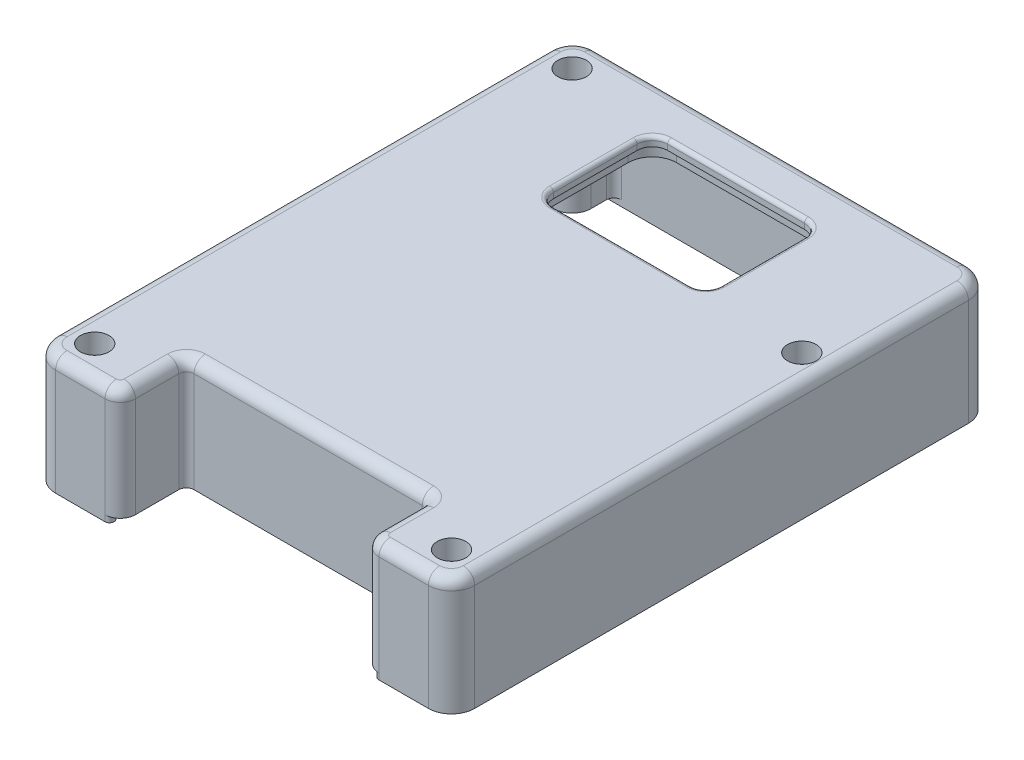
SolidWorks part; units mm, degrees
ref_plane "Front Plane" through (0, 0, 0) normal (0, 0, 1) x (1, 0, 0)
ref_plane "Top Plane" through (0, 0, 0) normal (0, 1, 0) x (1, 0, 0)
ref_plane "Right Plane" through (0, 0, 0) normal (1, 0, 0) x (0, 0, -1)
sketch "Esquisse1" plane through (0, 0, 0) normal (0, 1, 0) x (1, 0, 0)
  line L0 (-20.9, 31.3) -> (-20.9, 33.3)
  line L1 (-19.9, 34.3) -> (23.35, 34.3)
  line L2 (-26.35, 27.8) -> (-26.35, -27.9)
  line L3 (-19.95, -34.3) -> (-18.2, -34.3)
  line L4 (26.35, 31.3) -> (26.35, 17.55)
  line L5 (-26.35, 34.3) -> (26.35, -34.3) construction
  line L6 (-26.35, -34.3) -> (26.35, 34.3) construction
  line L7 (-24.5, 35.5) -> (24.5, 35.5)
  line L8 (-27.55, 32.45) -> (-27.55, -32.45)
  line L9 (-24.5, -35.5) -> (-18, -35.5)
  line L10 (27.55, 32.45) -> (27.55, -32.45)
  line L11 (-23.4, 28.8) -> (-25.35, 28.8)
  line L12 (20.95, -31.4) -> (20.95, -33.3)
  line L13 (23.45, -28.9) -> (25.35, -28.9)
  line L14 (-20.95, -31.4) -> (-20.95, -33.3)
  line L15 (-23.45, -28.9) -> (-25.35, -28.9)
  line L16 (24.05, 16.55) -> (25.35, 16.55)
  line L17 (24.05, 11.55) -> (25.35, 11.55)
  line L18 (26.35, 10.55) -> (26.35, -27.9)
  line L19 (0, 0) -> (0, -34.3) construction
  line L20 (0, -26.8) -> (15, -26.8)
  line L21 (0, -26.8) -> (-15, -26.8)
  line L22 (-16, -27.8) -> (-16, -33.5)
  line L23 (16, -27.8) -> (16, -33.5)
  line L24 (18, -35.5) -> (24.5, -35.5)
  line L25 (18.2, -34.3) -> (19.95, -34.3)
  line L26 (-17.2, -33.3) -> (-17.2, -26.6)
  line L27 (-16.2, -25.6) -> (16.2, -25.6)
  line L28 (17.2, -26.6) -> (17.2, -33.3)
  circle A0 centre (-23.45, -31.4) radius 1.1
  circle A1 centre (23.45, -31.4) radius 1.1
  circle A2 centre (-23.4, 31.3) radius 1.1
  circle A3 centre (24.05, 14.05) radius 1.1
  arc A4 (-23.4, 28.8) -> (-20.9, 31.3) centre (-23.4, 31.3) ccw
  arc A5 (-20.95, -31.4) -> (-23.45, -28.9) centre (-23.45, -31.4) ccw
  arc A6 (23.45, -28.9) -> (20.95, -31.4) centre (23.45, -31.4) ccw
  arc A7 (24.05, 16.55) -> (24.05, 11.55) centre (24.05, 14.05) ccw
  arc A8 (-27.55, -32.45) -> (-24.5, -35.5) centre (-24.5, -32.45) ccw
  arc A9 (24.5, -35.5) -> (27.55, -32.45) centre (24.5, -32.45) ccw
  arc A10 (24.5, 35.5) -> (27.55, 32.45) centre (24.5, 32.45) cw
  arc A11 (-24.5, 35.5) -> (-27.55, 32.45) centre (-24.5, 32.45) ccw
  arc A12 (23.35, 34.3) -> (26.35, 31.3) centre (23.35, 31.3) cw
  arc A13 (-25.35, 28.8) -> (-26.35, 27.8) centre (-25.35, 27.8) ccw
  arc A14 (-20.9, 33.3) -> (-19.9, 34.3) centre (-19.9, 33.3) cw
  arc A15 (25.35, -28.9) -> (26.35, -27.9) centre (25.35, -27.9) ccw
  arc A16 (20.95, -33.3) -> (19.95, -34.3) centre (19.95, -33.3) cw
  arc A17 (-20.95, -33.3) -> (-19.95, -34.3) centre (-19.95, -33.3) ccw
  arc A18 (-25.35, -28.9) -> (-26.35, -27.9) centre (-25.35, -27.9) cw
  arc A19 (25.35, 11.55) -> (26.35, 10.55) centre (25.35, 10.55) cw
  arc A20 (25.35, 16.55) -> (26.35, 17.55) centre (25.35, 17.55) ccw
  arc A21 (-17.2, -33.3) -> (-18.2, -34.3) centre (-18.2, -33.3) cw
  arc A22 (17.2, -33.3) -> (18.2, -34.3) centre (18.2, -33.3) ccw
  arc A23 (16, -33.5) -> (18, -35.5) centre (18, -33.5) ccw
  arc A24 (-16, -33.5) -> (-18, -35.5) centre (-18, -33.5) cw
  arc A25 (-17.2, -26.6) -> (-16.2, -25.6) centre (-16.2, -26.6) cw
  arc A26 (16.2, -25.6) -> (17.2, -26.6) centre (16.2, -26.6) cw
  arc A27 (15, -26.8) -> (16, -27.8) centre (15, -27.8) cw
  arc A28 (-15, -26.8) -> (-16, -27.8) centre (-15, -27.8) ccw
  point P0 (0, 0)
  point P59 (26.35, 11.55)
  point P79 (16, -35.5)
  dimension "D7" = 2.2
  dimension "D8" = 2.2
  dimension "D9" = 2.2
  dimension "D10" = 2.2
  dimension "D19" = 5
  dimension "D20" = 5
  dimension "D21" = 5
  dimension "D22" = 5
  dimension "D23" = 3.05
  dimension "D24" = 3
  dimension "D25" = 1
  dimension "D34" = 1
  dimension "D35" = 2
  dimension "D36" = 1
  dimension "D1" = 52.7
  dimension "D2" = 68.6
  dimension "D3" = 1.2
  dimension "D4" = 1.2
  dimension "D5" = 1.2
  dimension "D6" = 1.2
  dimension "D11" = 2.9
  dimension "D12" = 2.9
  dimension "D13" = 2.9
  dimension "D14" = 2.9
  dimension "D15" = 48.35
  dimension "D16" = 2.3
  dimension "D17" = 2.95
  dimension "D18" = 3
  dimension "D28" = 7.5
  dimension "D29" = 11.55
  dimension "D30" = 11.55
  dimension "D31" = 1.2
  dimension "D32" = 1.2
  dimension "D33" = 1.2
extrude "Boss.-Extru.1" add sketch "Esquisse1" along normal blind 13.5
sketch "Esquisse2" plane through (0, 13.5, 0) normal (0, 1, 0) x (1, 0, 0)
  line L16 (-24.5, -35.5) -> (-18, -35.5)
  line L17 (-16, -33.5) -> (-16, -27.8)
  line L18 (-15, -26.8) -> (15, -26.8)
  line L19 (16, -27.8) -> (16, -33.5)
  line L20 (18, -35.5) -> (24.5, -35.5)
  line L21 (27.55, -32.45) -> (27.55, 32.45)
  line L22 (24.5, 35.5) -> (-24.5, 35.5)
  line L23 (-27.55, 32.45) -> (-27.55, -32.45)
  line L24 (-24.5, -35.5) -> (-18, -35.5)
  line L25 (-16, -33.5) -> (-16, -27.8)
  line L26 (-15, -26.8) -> (15, -26.8)
  line L27 (16, -27.8) -> (16, -33.5)
  line L28 (18, -35.5) -> (24.5, -35.5)
  line L29 (27.55, -32.45) -> (27.55, 32.45)
  line L30 (24.5, 35.5) -> (-24.5, 35.5)
  line L31 (-27.55, 32.45) -> (-27.55, -32.45)
  arc A16 (-27.55, -32.45) -> (-24.5, -35.5) centre (-24.5, -32.45) ccw
  arc A17 (-18, -35.5) -> (-16, -33.5) centre (-18, -33.5) ccw
  arc A18 (-15, -26.8) -> (-16, -27.8) centre (-15, -27.8) ccw
  arc A19 (16, -27.8) -> (15, -26.8) centre (15, -27.8) ccw
  arc A20 (16, -33.5) -> (18, -35.5) centre (18, -33.5) ccw
  arc A21 (24.5, -35.5) -> (27.55, -32.45) centre (24.5, -32.45) ccw
  arc A22 (27.55, 32.45) -> (24.5, 35.5) centre (24.5, 32.45) ccw
  arc A23 (-24.5, 35.5) -> (-27.55, 32.45) centre (-24.5, 32.45) ccw
  arc A24 (-27.55, -32.45) -> (-24.5, -35.5) centre (-24.5, -32.45) ccw
  arc A25 (-18, -35.5) -> (-16, -33.5) centre (-18, -33.5) ccw
  arc A26 (-15, -26.8) -> (-16, -27.8) centre (-15, -27.8) ccw
  arc A27 (16, -27.8) -> (15, -26.8) centre (15, -27.8) ccw
  arc A28 (16, -33.5) -> (18, -35.5) centre (18, -33.5) ccw
  arc A29 (24.5, -35.5) -> (27.55, -32.45) centre (24.5, -32.45) ccw
  arc A30 (27.55, 32.45) -> (24.5, 35.5) centre (24.5, 32.45) ccw
  arc A31 (-24.5, 35.5) -> (-27.55, 32.45) centre (-24.5, 32.45) ccw
  dimension "D1" = 0
extrude "Boss.-Extru.2" add sketch "Esquisse2" along normal blind 1.2
fillet "Congé1" radius 1.5 16 edges at (-27.55, 14.7, 0) (-26.6567, 14.7, -34.6067) (0, 14.7, -35.5) (26.6567, 14.7, -34.6067) (27.55, 14.7, 0) (26.6567, 14.7, 34.6067) (21.25, 14.7, 35.5) (16.5858, 14.7, 34.9142) (16, 14.7, 30.65) (15.7071, 14.7, 27.0929) (0, 14.7, 26.8) (-15.7071, 14.7, 27.0929) (-16, 14.7, 30.65) (-16.5858, 14.7, 34.9142) (-21.25, 14.7, 35.5) (-26.6567, 14.7, 34.6067)
sketch "Esquisse3" plane through (0, 0, 0) normal (0, -1, 0) x (1, 0, 0)
  line L8 (-26.35, 32.45) -> (-26.35, -32.45)
  line L9 (-24.5, -34.3) -> (24.5, -34.3)
  line L10 (26.35, -32.45) -> (26.35, 32.45)
  line L11 (24.5, 34.3) -> (18, 34.3)
  line L12 (17.2, 33.5) -> (17.2, 27.8)
  line L13 (15, 25.6) -> (-15, 25.6)
  line L14 (-17.2, 27.8) -> (-17.2, 33.5)
  line L15 (-18, 34.3) -> (-24.5, 34.3)
  line L16 (-27.55, 32.45) -> (-27.55, -32.45)
  line L17 (-24.5, -35.5) -> (24.5, -35.5)
  line L18 (27.55, -32.45) -> (27.55, 32.45)
  line L19 (24.5, 35.5) -> (18, 35.5)
  line L20 (16, 33.5) -> (16, 27.8)
  line L21 (15, 26.8) -> (-15, 26.8)
  line L22 (-16, 27.8) -> (-16, 33.5)
  line L23 (-18, 35.5) -> (-24.5, 35.5)
  line L24 (-27.55, 32.45) -> (-27.55, -32.45)
  line L25 (-24.5, -35.5) -> (24.5, -35.5)
  line L26 (27.55, -32.45) -> (27.55, 32.45)
  line L27 (24.5, 35.5) -> (18, 35.5)
  line L28 (16, 33.5) -> (16, 27.8)
  line L29 (15, 26.8) -> (-15, 26.8)
  line L30 (-16, 27.8) -> (-16, 33.5)
  line L31 (-18, 35.5) -> (-24.5, 35.5)
  arc A8 (-26.35, -32.45) -> (-24.5, -34.3) centre (-24.5, -32.45) ccw
  arc A9 (24.5, -34.3) -> (26.35, -32.45) centre (24.5, -32.45) ccw
  arc A10 (26.35, 32.45) -> (24.5, 34.3) centre (24.5, 32.45) ccw
  arc A11 (18, 34.3) -> (17.2, 33.5) centre (18, 33.5) ccw
  arc A12 (15, 25.6) -> (17.2, 27.8) centre (15, 27.8) ccw
  arc A13 (-17.2, 27.8) -> (-15, 25.6) centre (-15, 27.8) ccw
  arc A14 (-17.2, 33.5) -> (-18, 34.3) centre (-18, 33.5) ccw
  arc A15 (-24.5, 34.3) -> (-26.35, 32.45) centre (-24.5, 32.45) ccw
  arc A16 (-24.5, 35.5) -> (-27.55, 32.45) centre (-24.5, 32.45) ccw
  arc A17 (-27.55, -32.45) -> (-24.5, -35.5) centre (-24.5, -32.45) ccw
  arc A18 (24.5, -35.5) -> (27.55, -32.45) centre (24.5, -32.45) ccw
  arc A19 (27.55, 32.45) -> (24.5, 35.5) centre (24.5, 32.45) ccw
  arc A20 (18, 35.5) -> (16, 33.5) centre (18, 33.5) ccw
  arc A21 (15, 26.8) -> (16, 27.8) centre (15, 27.8) ccw
  arc A22 (-16, 27.8) -> (-15, 26.8) centre (-15, 27.8) ccw
  arc A23 (-16, 33.5) -> (-18, 35.5) centre (-18, 33.5) ccw
  arc A24 (-24.5, 35.5) -> (-27.55, 32.45) centre (-24.5, 32.45) ccw
  arc A25 (-27.55, -32.45) -> (-24.5, -35.5) centre (-24.5, -32.45) ccw
  arc A26 (24.5, -35.5) -> (27.55, -32.45) centre (24.5, -32.45) ccw
  arc A27 (27.55, 32.45) -> (24.5, 35.5) centre (24.5, 32.45) ccw
  arc A28 (18, 35.5) -> (16, 33.5) centre (18, 33.5) ccw
  arc A29 (15, 26.8) -> (16, 27.8) centre (15, 27.8) ccw
  arc A30 (-16, 27.8) -> (-15, 26.8) centre (-15, 27.8) ccw
  arc A31 (-16, 33.5) -> (-18, 35.5) centre (-18, 33.5) ccw
  dimension "D1" = 0
  dimension "D2" = 1.2
extrude "Boss.-Extru.3" add sketch "Esquisse3" along normal blind 0.8
sketch "Esquisse4" plane through (0, -0.8, 0) normal (0, -1, 0) x (-1, 0, 0)
  line L0 (18, -34.3) -> (24.5, -34.3) construction
  line L1 (18.8331, -34.3) -> (-18.8435, -34.3)
  line L2 (18.8331, -34.3) -> (18.8331, -23.8135)
  line L3 (18.8331, -23.8135) -> (-18.8435, -23.8135)
  line L4 (-18.8435, -34.3) -> (-18.8435, -23.8135)
extrude "Enlèv. mat.-Extru.1" cut sketch "Esquisse4" against normal blind 0.8
fillet "Congé2" radius 0.6 2 edges at (16.167, -0.4, 34.3) (-16.167, -0.4, 34.3)
sketch "Esquisse5" plane through (0, 13.5, 0) normal (0, -1, 0) x (1, 0, 0)
  circle A0 centre (-23.45, 31.4) radius 1.25
  circle A1 centre (23.45, 31.4) radius 1.25
  circle A2 centre (24.05, -14.05) radius 1.25
  circle A3 centre (-23.4, -31.3) radius 1.25
extrude "Enlèv. mat.-Extru.2" cut sketch "Esquisse5" against normal through all
sketch "Esquisse6" plane through (0, 14.7, 0) normal (0, 1, 0) x (1, 0, 0)
  circle A0 centre (-23.4, 31.3) radius 1.875
  circle A1 centre (24.05, 14.05) radius 1.875
  circle A2 centre (23.45, -31.4) radius 1.875
  circle A3 centre (-23.45, -31.4) radius 1.875
  dimension "D1" = 3.75
  dimension "D2" = 3.75
  dimension "D3" = 3.75
  dimension "D4" = 3.75
extrude "Enlèv. mat.-Extru.3" cut sketch "Esquisse6" against normal blind 3.3
fillet "Congé3" radius 0.6 34 edges at (24.7, 13.5, -11.55) (26.0571, 13.5, -11.2571) (26.35, 13.5, 8.675) (26.0571, 13.5, 28.6071) (24.4, 13.5, 28.9) (21.6822, 13.5, 29.6322) (20.95, 13.5, 32.35) (20.6571, 13.5, 34.0071) (19.075, 13.5, 34.3) (17.4929, 13.5, 34.0071) (17.2, 13.5, 29.95) (16.9071, 13.5, 25.8929) (0, 13.5, 25.6) (-16.9071, 13.5, 25.8929) (-17.2, 13.5, 29.95) (-17.4929, 13.5, 34.0071) (-19.075, 13.5, 34.3) (-20.6571, 13.5, 34.0071) (-20.95, 13.5, 32.35) (-21.6822, 13.5, 29.6322) (-24.4, 13.5, 28.9) (-26.0571, 13.5, 28.6071) (-26.35, 13.5, 0.05) (-26.0571, 13.5, -28.5071) (-24.375, 13.5, -28.8) (-21.6322, 13.5, -29.5322) (-20.9, 13.5, -32.3) (-20.6071, 13.5, -34.0071) (1.725, 13.5, -34.3) (25.4713, 13.5, -33.4213) (26.35, 13.5, -24.425) (26.0571, 13.5, -16.8429) (24.7, 13.5, -16.55) (21.55, 13.5, -14.05)
fillet "Congé4" radius 0.7 4 edges at (-23.45, 11.4, 33.275) (23.45, 11.4, 33.275) (-23.4, 11.4, -29.425) (24.05, 11.4, -12.175)
sketch "Esquisse7" plane through (0, 13.5, 0) normal (0, -1, 0) x (1, 0, 0)
  line L0 (0, 0) -> (0, -34.3) construction
  line L1 (23.35, -34.3) -> (-19.9, -34.3) construction
  line L3 (-9, -14.45) -> (9, -14.45)
  line L4 (-11, -16.45) -> (-11, -27.45)
  line L5 (-9, -29.45) -> (9, -29.45)
  line L6 (11, -16.45) -> (11, -27.45)
  line L7 (-11, -14.45) -> (11, -29.45) construction
  line L8 (-11, -29.45) -> (11, -14.45) construction
  arc A0 (9, -14.45) -> (11, -16.45) centre (9, -16.45) cw
  arc A1 (9, -29.45) -> (11, -27.45) centre (9, -27.45) ccw
  arc A2 (-11, -27.45) -> (-9, -29.45) centre (-9, -27.45) ccw
  arc A3 (-9, -14.45) -> (-11, -16.45) centre (-9, -16.45) ccw
  point P5 (0, -21.95)
  dimension "D4" = 2
  dimension "D1" = 12.35
  dimension "D2" = 15
  dimension "D3" = 22
extrude "Enlèv. mat.-Extru.4" cut sketch "Esquisse7" against normal blind 10
sketch "Esquisse8" plane through (0, 13.5, 0) normal (0, -1, 0) x (1, 0, 0)
  line L20 (-13.4, -16.45) -> (-13.4, -27.45)
  line L21 (-9, -31.85) -> (9, -31.85)
  line L22 (13.4, -27.45) -> (13.4, -16.45)
  line L23 (9, -12.05) -> (-9, -12.05)
  line L24 (-9, -30.65) -> (9, -30.65)
  line L25 (12.2, -27.45) -> (12.2, -16.45)
  line L26 (9, -13.25) -> (-9, -13.25)
  line L27 (-12.2, -16.45) -> (-12.2, -27.45)
  line L28 (-9, -30.65) -> (9, -30.65)
  line L29 (12.2, -27.45) -> (12.2, -16.45)
  line L30 (9, -13.25) -> (-9, -13.25)
  line L31 (-12.2, -16.45) -> (-12.2, -27.45)
  arc A16 (-13.4, -27.45) -> (-9, -31.85) centre (-9, -27.45) ccw
  arc A17 (9, -31.85) -> (13.4, -27.45) centre (9, -27.45) ccw
  arc A18 (13.4, -16.45) -> (9, -12.05) centre (9, -16.45) ccw
  arc A19 (-9, -12.05) -> (-13.4, -16.45) centre (-9, -16.45) ccw
  arc A20 (9, -30.65) -> (12.2, -27.45) centre (9, -27.45) ccw
  arc A21 (-12.2, -27.45) -> (-9, -30.65) centre (-9, -27.45) ccw
  arc A22 (12.2, -16.45) -> (9, -13.25) centre (9, -16.45) ccw
  arc A23 (-9, -13.25) -> (-12.2, -16.45) centre (-9, -16.45) ccw
  arc A24 (9, -30.65) -> (12.2, -27.45) centre (9, -27.45) ccw
  arc A25 (-12.2, -27.45) -> (-9, -30.65) centre (-9, -27.45) ccw
  arc A26 (12.2, -16.45) -> (9, -13.25) centre (9, -16.45) ccw
  arc A27 (-9, -13.25) -> (-12.2, -16.45) centre (-9, -16.45) ccw
  dimension "D1" = 1.2
  dimension "D2" = 1.2
extrude "Boss.-Extru.4" add sketch "Esquisse8" along normal blind 2 contours L20 A16 L21 A17 L22 A18 L23 A19 | A24 L29 A26 L30 A27 L31 A25 L28
fillet "Congé5" radius 0.5 8 edges at (10.4142, 14.7, -15.0358) (0, 14.7, -14.45) (-10.4142, 14.7, -15.0358) (-11, 14.7, -21.95) (-10.4142, 14.7, -28.8642) (0, 14.7, -29.45) (10.4142, 14.7, -28.8642) (11, 14.7, -21.95)
